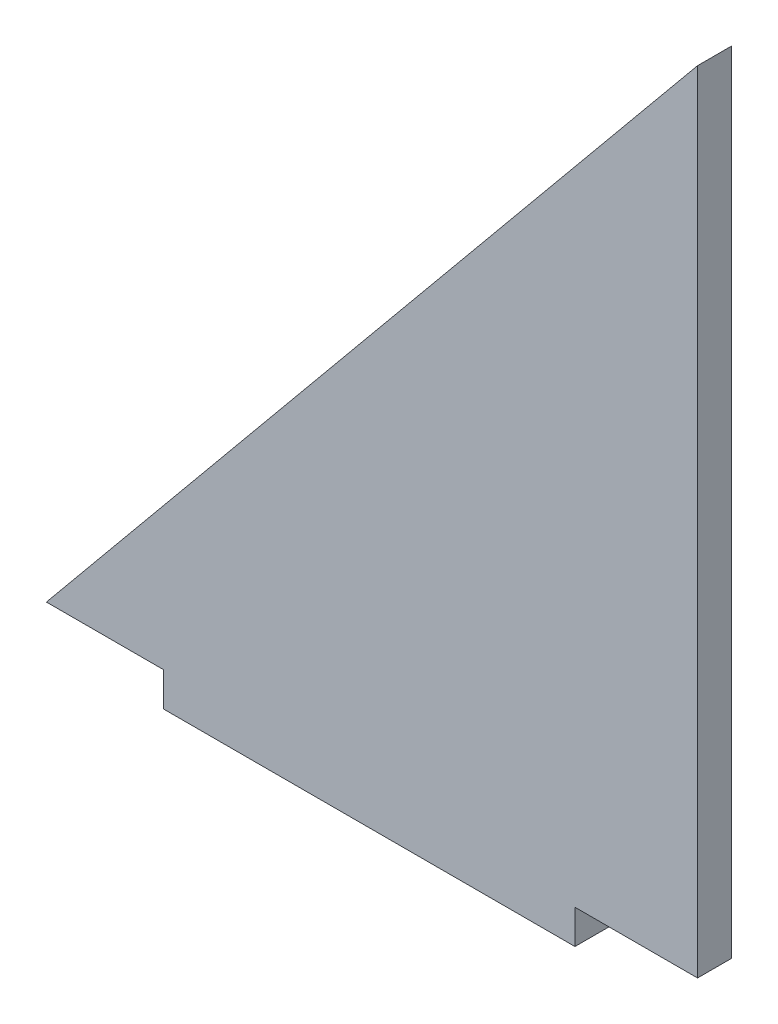
SolidWorks part; units mm, degrees
ref_plane "Front Plane" through (0, 0, 0) normal (0, 0, 1) x (1, 0, 0)
ref_plane "Top Plane" through (0, 0, 0) normal (0, 1, 0) x (1, 0, 0)
ref_plane "Right Plane" through (0, 0, 0) normal (1, 0, 0) x (0, 0, -1)
sketch "Sketch1" plane through (0, 0, 0) normal (0, 0, 1) x (1, 0, 0)
  line L0 (-60.706, 0) -> (-49.784, 0) construction
  line L1 (-60.706, 0) -> (0, 73.66)
  line L2 (0, 73.66) -> (0, 0)
  line L3 (0, 0) -> (-11.43, 0)
  line L5 (-49.784, 0) -> (-49.784, -3.175)
  line L6 (-49.784, -3.175) -> (-11.43, -3.175)
  line L7 (-11.43, 0) -> (-11.43, -3.175)
  line L8 (-49.784, 0) -> (-60.706, 0)
  line L9 (-11.43, 0) -> (0, 0) construction
  dimension "D1" = 3.175
  dimension "D2" = 38.354
  dimension "D3" = 11.43
  dimension "D4" = 73.66
  dimension "D5" = 10.922
extrude "Boss-Extrude1" add sketch "Sketch1" along normal blind 3.175
